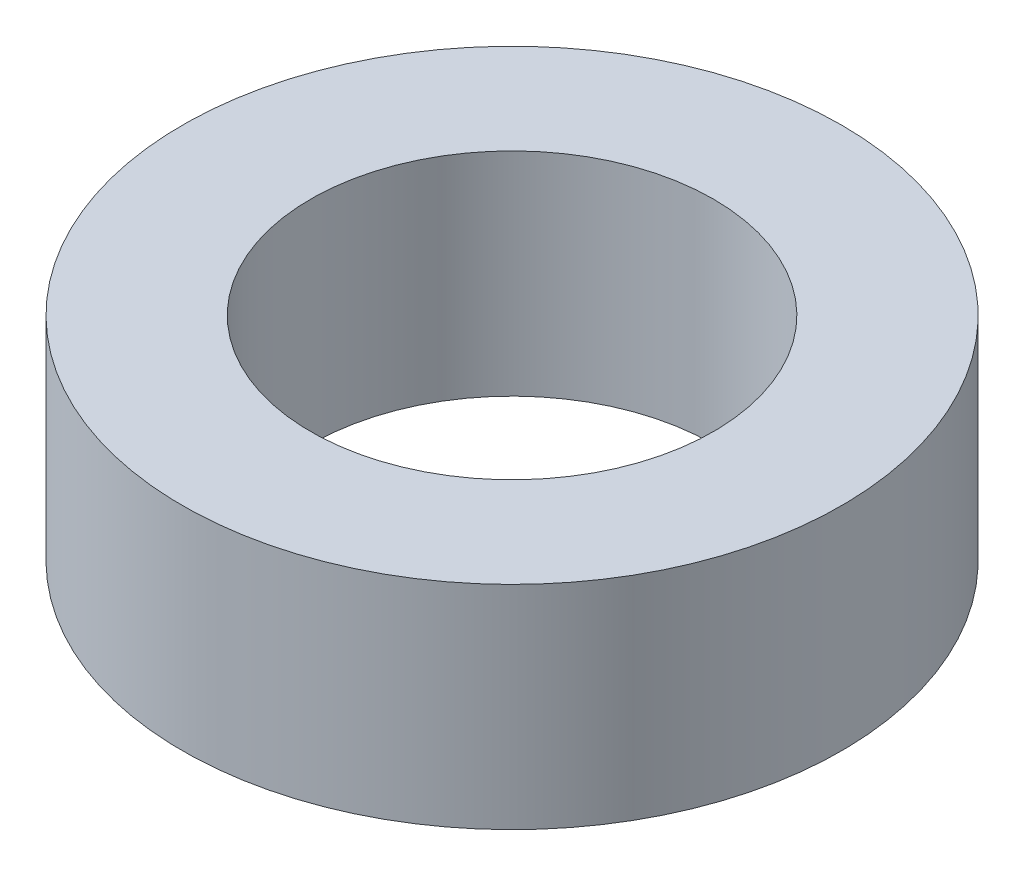
SolidWorks part; units mm, degrees
ref_plane "Front Plane" through (0, 0, 0) normal (0, 0, 1) x (1, 0, 0)
ref_plane "Top Plane" through (0, 0, 0) normal (0, 1, 0) x (1, 0, 0)
ref_plane "Right Plane" through (0, 0, 0) normal (1, 0, 0) x (0, 0, -1)
sketch "Sketch1" plane through (0, 0, 0) normal (0, 1, 0) x (1, 0, 0)
  circle A0 centre (0, 0) radius 45
  dimension "FLANGE_OD" = 90
extrude "Boss-Extrude1" add sketch "Sketch1" along normal blind 29
sketch "Sketch2" plane through (0, 0, 0) normal (0, 1, 0) x (1, 0, 0)
  circle A0 centre (0, 0) radius 27.5
  dimension "BORE_D" = 55
extrude "Cut-Extrude1" cut sketch "Sketch2" along normal through all
sketch "Sketch3" plane through (0, 29, 0) normal (0, 1, 0) x (1, 0, 0)
  circle A0 centre (0, 0) radius 19.112 construction
  circle A1 centre (-19.112, 0) radius 3.0336
  dimension "BOLT_D" = 6.0672
  dimension "BOLT_PCD" = 38.224
extrude "Cut-Extrude2" cut sketch "Sketch3" against normal blind 23.7236 rebuild error yes
pattern_circular "CirPattern1" count 6 over 360 rebuild error yes
